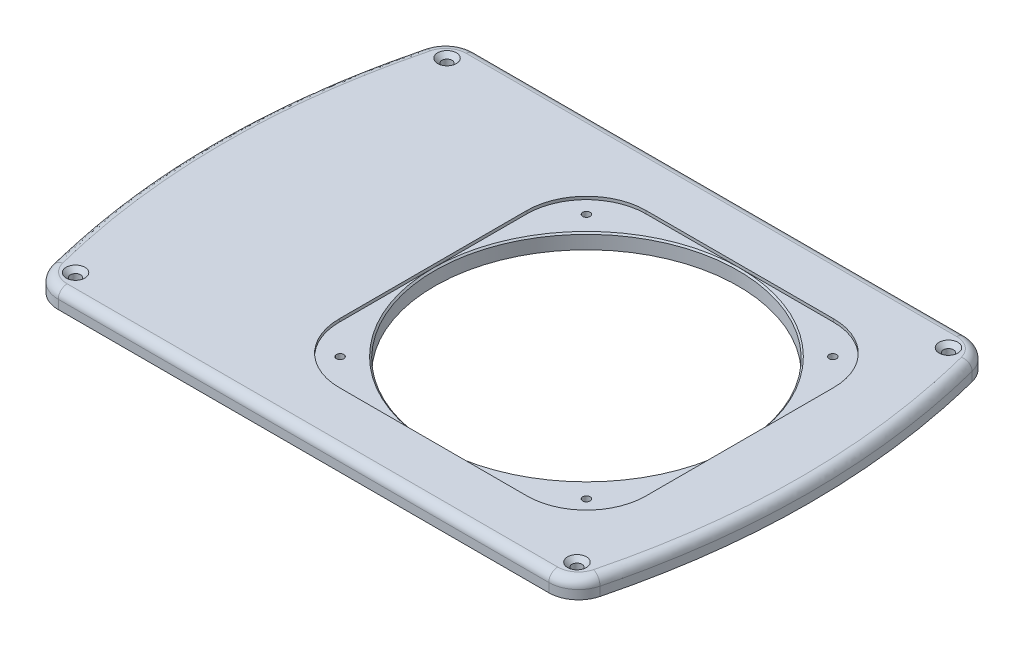
SolidWorks part; units mm, degrees
ref_plane "Front Plane" through (0, 0, 0) normal (0, 0, 1) x (1, 0, 0)
ref_plane "Top Plane" through (0, 0, 0) normal (0, 1, 0) x (1, 0, 0)
ref_plane "Right Plane" through (0, 0, 0) normal (1, 0, 0) x (0, 0, -1)
sketch "Sketch1" plane through (0, 0, 0) normal (0, 1, 0) x (1, 0, 0)
  line L0 (-100, 80) -> (-100, -80) construction
  line L1 (-90, 70) -> (90, 70)
  line L2 (-90, 70) -> (-90, -70) construction
  line L3 (-90, -70) -> (90, -70)
  line L4 (90, 70) -> (90, -70) construction
  line L5 (-90, 70) -> (90, -70) construction
  line L6 (-90, -70) -> (90, 70) construction
  line L8 (100, 80) -> (100, -80) construction
  line L10 (-100, -80) -> (100, -80) construction
  line L11 (-100, 80) -> (100, 80) construction
  spline S0 degree 2 poles (-90, 70) (-110, 0) (-90, -70) knots 0 0 0 1 1 1
  spline S1 degree 2 poles (90, 70) (110, 0) (90, -70) knots 0 0 0 1 1 1
  point P0 (0, 0)
  dimension "D1" = 180
  dimension "D2" = 140
  dimension "D3" = 10
extrude "Boss-Extrude1" add sketch "Sketch1" along normal blind 6
fillet "Fillet1" radius 10 4 edges at (-90, 3, -70) (90, 3, -70) (90, 3, 70) (-90, 3, 70)
fillet "Fillet2" radius 3 8 edges at (-88.4812, 6, -67.8964) (0, 6, -70) (88.4812, 6, -67.8964) (88.4812, 6, 67.8964) (0, 6, 70) (-88.4812, 6, 67.8964)
sketch "Sketch2" plane through (0, 6, 0) normal (0, 1, 0) x (1, 0, 0)
  line L0 (-82.3456, 60) -> (-88.4812, 67.8964) construction
  line L1 (82.3456, 60) -> (88.4812, 67.8964) construction
  line L2 (82.3456, -60) -> (88.4812, -67.8964) construction
  line L3 (-82.3456, -60) -> (-88.4812, -67.8964) construction
  line L4 (76, 51) -> (-26, 51) construction
  line L5 (-26, -51) -> (76, -51) construction
  line L6 (-26, -51) -> (-26, 51) construction
  line L7 (76, -51) -> (76, 51) construction
  line L8 (-26, -51.5) -> (76, -51.5) construction
  line L9 (-26.5, -51.5) -> (-26.5, 51.5)
  line L10 (76.5, 51.5) -> (-26.5, 51.5)
  line L11 (76.5, -51.5) -> (76.5, 51.5)
  line L12 (-26.5, -51.5) -> (76.5, -51.5)
  line L13 (-26.5, -51) -> (-26.5, 51) construction
  line L14 (76.5, -51) -> (76.5, 51) construction
  line L15 (76, 51.5) -> (-26, 51.5) construction
  arc A6 (-82.3456, 70) -> (-92.0355, 62.4708) centre (-82.3456, 60) ccw construction
  arc A7 (92.0355, 62.4708) -> (82.3456, 70) centre (82.3456, 60) ccw construction
  arc A8 (82.3456, -70) -> (92.0355, -62.4708) centre (82.3456, -60) ccw construction
  arc A9 (-92.0355, -62.4708) -> (-82.3456, -70) centre (-82.3456, -60) ccw construction
  circle A10 centre (25, 0) radius 51
  circle A11 centre (25, 0) radius 58.5 construction
  circle A12 centre (25, 0) radius 67 construction
  point P14 (66.3657, 41.3657)
  point P15 (83.5, 0)
  point P19 (66.3657, -41.3657)
  point P20 (-16.3657, -41.3657)
  point P24 (-16.3657, 41.3657)
  point P25 (25, 0)
  point P36 (-84.1863, 62.3689)
  point P37 (84.1863, 62.3689)
  point P50 (84.1863, -62.3689)
  point P57 (-84.1863, -62.3689)
  dimension "D2" = 102
  dimension "D3" = 25
  dimension "D4" = 134
  dimension "D5" = 117
  dimension "D6" = 45
  dimension "D7" = 4
  dimension "D8" = 45
  dimension "D10" = 0.5
  dimension "D11" = 0.5
  dimension "D16" = 7
  dimension "D17" = 7
  dimension "D18" = 7
  dimension "D19" = 7
  dimension "D9" = 58.5
extrude "Cut-Extrude1" cut sketch "Sketch2" against normal up to next contours A10
hole_wizard "M3x0.5 Tapped Hole1" positions "Sketch16" profile "Sketch17" tap size "M3x0.5" standard "ANSI Metric" end condition up to next
sketch "Sketch16" plane through (0, 6, 0) normal (0, 1, 0) x (1, 0, 0)
  point P0 (66.3657, 41.3657)
  point P3 (66.3657, -41.3657)
  point P6 (-16.3657, -41.3657)
  point P9 (-16.3657, 41.3657)
sketch "Sketch17" plane through (66.3657, 6, -41.3657) normal (1, 0, 0) x (0, 0, 1)
  line L0 (0, 0) -> (0, 6)
  line L1 (0, 6) -> (1.25, 6)
  line L2 (1.25, 6) -> (1.25, 0)
  line L5 (1.25, 0) -> (0, 0)
  line L11 (0, -6.35) -> (0, 107.95) construction
  dimension "Thread Major Dia." = 2.5
  dimension "Thru Tap Drill Depth" = 6
hole_wizard "CSK for M3 Flat Head Machine Screw6" positions "Sketch14" profile "Sketch15" countersink size "M3" standard "ANSI Metric" end condition up to next
sketch "Sketch14" plane through (0, 6, 0) normal (0, 1, 0) x (1, 0, 0)
  point P0 (-84.1863, 62.3689)
  point P3 (84.1863, 62.3689)
  point P6 (84.1863, -62.3689)
  point P9 (-84.1863, -62.3689)
sketch "Sketch15" plane through (-84.1863, 6, -62.3689) normal (1, 0, 0) x (0, 0, 1)
  line L0 (0, 0) -> (0, 6)
  line L1 (0, 6) -> (1.7, 6)
  line L2 (1.7, 6) -> (1.7, 1.45)
  line L3 (1.7, 1.45) -> (3.15, 0)
  line L5 (3.15, 0) -> (0, 0)
  line L6 (-1.7, 1.45) -> (-3.15, 0) construction
  line L11 (0, -6.35) -> (0, 107.95) construction
  dimension "Thru Hole Dia." = 3.4
  dimension "Thru Hole Depth" = 6
  dimension "Near C'Sink Dia." = 6.3
  dimension "Near C'Sink Angle" = 90
extrude "Cut-Extrude3" cut sketch "Sketch2<7>" against normal blind 1 contours L9 L10 L11 L12
sketch "Sketch2<7>" plane through (0, 6, 0) normal (0, 1, 0) x (1, 0, 0) same geometry as "Sketch2"
fillet "Fillet4" radius 20 4 edges at (-26.5, 5.5, 51.5) (76.5, 5.5, 51.5) (76.5, 5.5, -51.5) (-26.5, 5.5, -51.5)
chamfer "Chamfer1" distance 0.5 angle 45 1 edges at (25, 5, 51)
